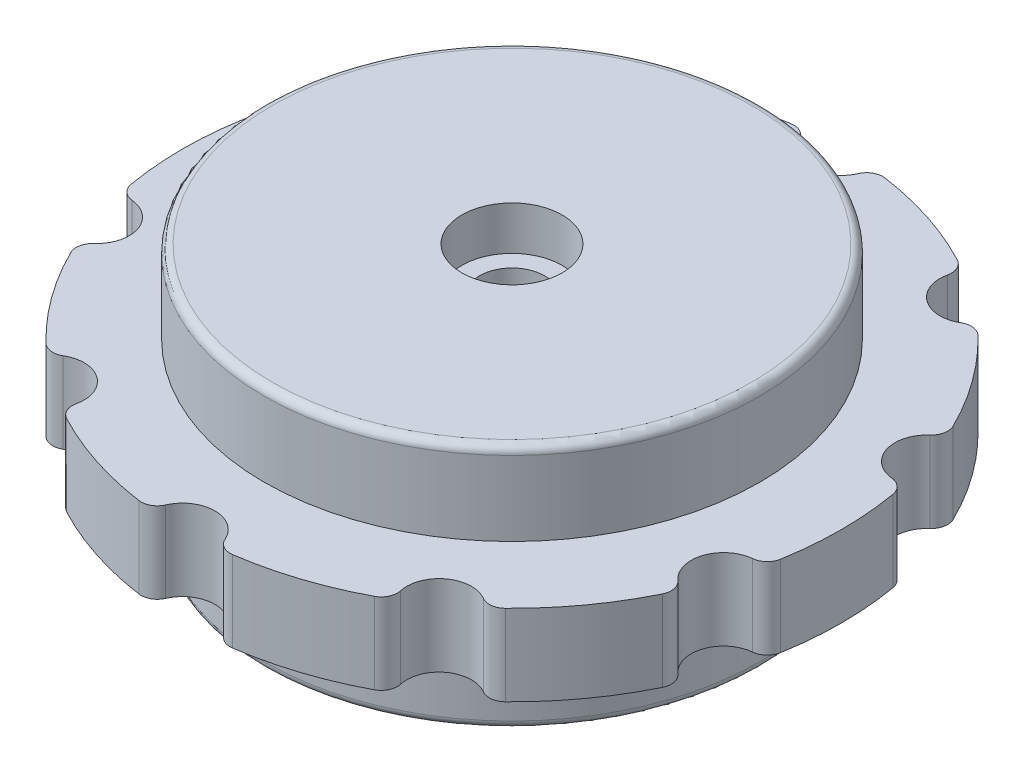
SolidWorks part; units mm, degrees
ref_plane "前视基准面" through (0, 0, 0) normal (0, 0, 1) x (1, 0, 0)
ref_plane "上视基准面" through (0, 0, 0) normal (0, 1, 0) x (1, 0, 0)
ref_plane "右视基准面" through (0, 0, 0) normal (1, 0, 0) x (0, 0, -1)
other "Configuration Table"
sketch "草图1" plane through (0, 0, 0) normal (0, 1, 0) x (1, 0, 0)
  circle A0 centre (0, 0) radius 15.3
  circle A1 centre (0, 0) radius 20.35
  circle A2 centre (0, 0) radius 13.7
  circle A3 centre (0, 20.35) radius 2
  dimension "D1" = 30.6
  dimension "D2" = 40.7
  dimension "D3" = 1.6
  dimension "D4" = 4
extrude "凸台-拉伸1" add sketch "草图1" along normal mid plane 15.2 contours A0 | A2
extrude "凸台-拉伸2" add sketch "草图1<3>" along normal mid plane 5 contours A1
sketch "草图1<3>" plane through (0, 0, 0) normal (0, 1, 0) x (1, 0, 0) same geometry as "草图1"
extrude "切除-拉伸1" cut sketch "草图1<4>" against normal through all both and the other way through all contours A3
sketch "草图1<4>" plane through (0, 0, 0) normal (0, 1, 0) x (1, 0, 0) same geometry as "草图1"
fillet "圆角1" radius 1 2 edges at (1.9976, 0, -20.2517) (-1.9976, 0, -20.2517)
pattern_circular "阵列(圆周)1" count 10 over 360 about axis through (0, 2.5, 0) along (0, -1, 0) of "切除-拉伸1", "圆角1"
fillet "圆角2" radius 0.5 2 edges at (0, -7.6, 15.3) (0, 7.6, 15.3)
extrude "凸台-拉伸3" add sketch "草图1<5>" along normal mid plane 7.8 contours A2
sketch "草图1<5>" plane through (0, 0, 0) normal (0, 1, 0) x (1, 0, 0) same geometry as "草图1"
extrude "凸台-拉伸5" add sketch "草图1<6>" along normal up to surface (7.6 mm away) from surface contours A2 up to face at (0, 7.6, 14.8) starting at face at (0, -7.6, 14.8)
sketch "草图1<6>" plane through (0, 0, 0) normal (0, 1, 0) x (1, 0, 0) same geometry as "草图1"
sketch "草图2" plane through (0, 2.5, 0) normal (0, 1, 0) x (1, 0, 0)
  line L0 (0, 20.35) -> (11.9614, 16.4635)
  line L1 (-11.9614, 16.4635) -> (0, 20.35)
  arc A0 (-1.834, 19.5523) -> (1.834, 19.5523) centre (0, 20.35) ccw construction
  arc A1 (10.0088, 16.8962) -> (12.9763, 14.7401) centre (11.9614, 16.4635) ccw construction
  arc A2 (-12.9763, 14.7401) -> (-10.0088, 16.8962) centre (-11.9614, 16.4635) ccw construction
  dimension "D1" = 12.577
  dimension "D2" = 12.577
sketch "草图4" plane through (0, -7.6, 0) normal (0, -1, 0) x (1, 0, 0)
  circle A0 centre (0, 0) radius 2
  circle A1 centre (0, 0) radius 3.1
  dimension "D1" = 4
  dimension "D2" = 6.2
extrude "切除-拉伸3" cut sketch "草图4" against normal through all contours A0
extrude "切除-拉伸4" cut sketch "草图4<3>" against normal blind 2.7 contours A1
sketch "草图4<3>" plane through (0, -7.6, 0) normal (0, -1, 0) x (1, 0, 0) same geometry as "草图4"
extrude "切除-拉伸5" cut sketch "草图4<4>" along normal blind 2.7 from surface contours A1 starting at face at (0, 7.6, -2)
sketch "草图4<4>" plane through (0, -7.6, 0) normal (0, -1, 0) x (1, 0, 0) same geometry as "草图4"
sketch "草图5" plane through (0, -7.6, 0) normal (0, -1, 0) x (1, 0, 0)
  circle A0 centre (0, 0) radius 13
  dimension "D1" = 26
extrude "切除-拉伸6" cut sketch "草图5" against normal blind 4.5
sketch "草图6" plane through (0, -3.1, 0) normal (0, -1, 0) x (1, 0, 0)
  circle A0 centre (0, 0) radius 3.1
  dimension "D1" = 6.2
extrude "切除-拉伸7" cut sketch "草图6" against normal blind 4.6
sketch "草图7" plane through (0, -3.1, 0) normal (0, -1, 0) x (1, 0, 0)
  circle A0 centre (-8, 0) radius 0.75
  circle A1 centre (4, 6.9282) radius 0.75
  circle A2 centre (4, -6.9282) radius 0.75
  point P9 (0, 0)
  dimension "D1" = 1.5
  dimension "D2" = 8
  dimension "D3" = 3
extrude "切除-拉伸8" cut sketch "草图7" against normal blind 5 contours A0 | A1 | A2
